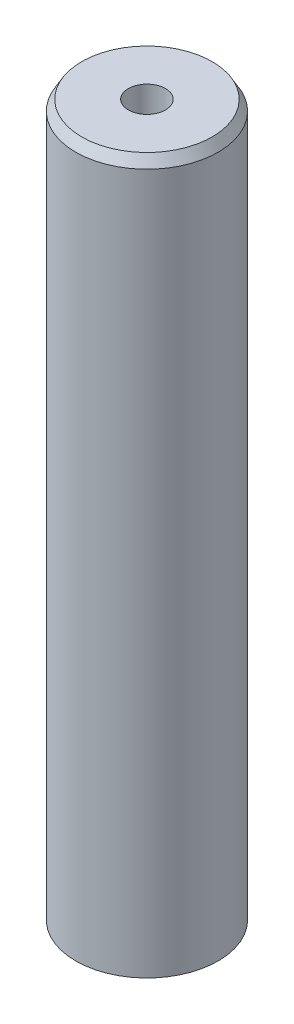
SolidWorks part; units mm, degrees
ref_plane "Front Plane" through (0, 0, 0) normal (0, 0, 1) x (1, 0, 0)
ref_plane "Top Plane" through (0, 0, 0) normal (0, 1, 0) x (1, 0, 0)
ref_plane "Right Plane" through (0, 0, 0) normal (1, 0, 0) x (0, 0, -1)
sketch "Sketch1" plane through (0, 0, 0) normal (0, 1, 0) x (1, 0, 0)
  circle A0 centre (0, 0) radius 7.5
  dimension "SHAFT_OD" = 15
extrude "Boss-Extrude1" add sketch "Sketch1" along normal blind 75.5117
sketch "Sketch2" plane through (0, 0, 0) normal (0, 1, 0) x (1, 0, 0)
  circle A0 centre (0, 0) radius 1.9586
  dimension "BORE_D" = 3.9171
extrude "Cut-Extrude1" cut sketch "Sketch2" along normal through all
chamfer "Chamfer1" distance 1.0843 angle 30 2 edges at (0, 75.5117, 7.5) (0, 0, 7.5) first distance on face at (0, 75.5117, 7.5) first distance on face at (0, 0, 1.9586)
